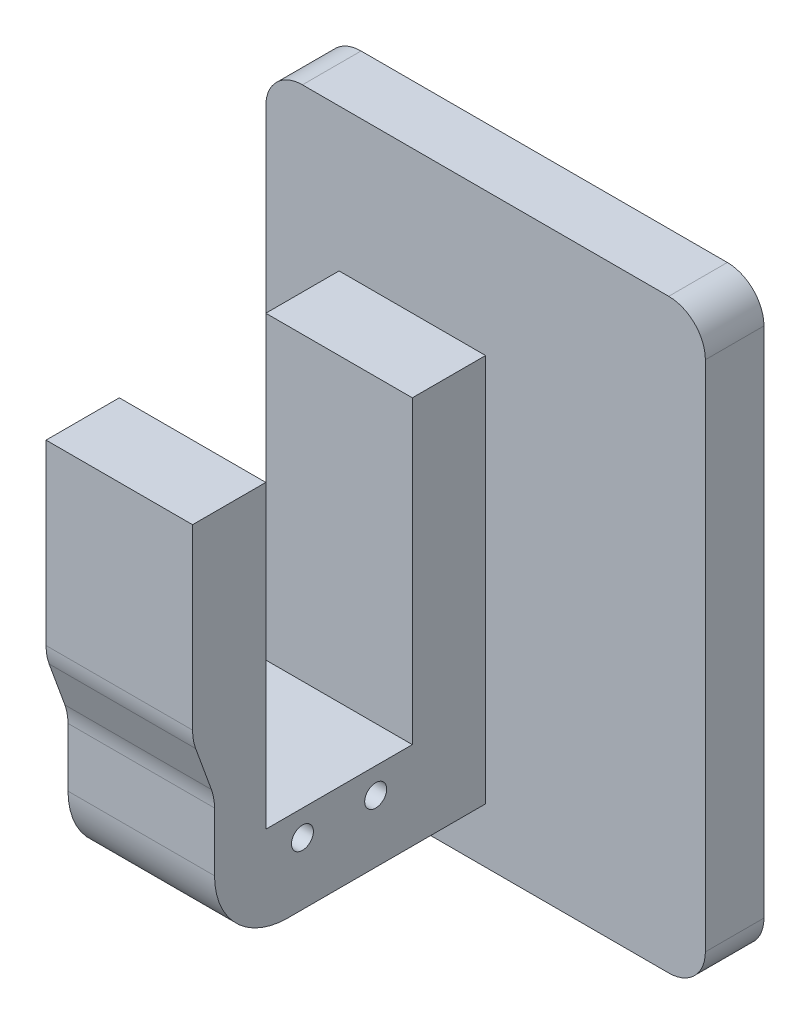
SolidWorks part; units mm, degrees
ref_plane "Front Plane" through (0, 0, 0) normal (0, 0, 1) x (1, 0, 0)
ref_plane "Top Plane" through (0, 0, 0) normal (0, 1, 0) x (1, 0, 0)
ref_plane "Right Plane" through (0, 0, 0) normal (1, 0, 0) x (0, 0, -1)
sketch "Sketch3" plane through (0, 0, 30) normal (0, 0, -1) x (-1, 0, 0)
  line L0 (95, 33.2573) -> (65, 33.2573) construction
  line L15 (80, 53.2573) -> (80, 33.2573) construction
  line L20 (55, 53.2573) -> (105, 53.2573)
  line L29 (55, -26.7427) -> (105, -26.7427)
  line L31 (110, -21.7427) -> (110, 48.2573)
  line L33 (50, -21.7427) -> (50, 48.2573)
  arc A17 (50, 48.2573) -> (55, 53.2573) centre (55, 48.2573) cw
  arc A18 (110, 48.2573) -> (105, 53.2573) centre (105, 48.2573) ccw
  arc A21 (50, -21.7427) -> (55, -26.7427) centre (55, -21.7427) ccw
  arc A22 (110, -21.7427) -> (105, -26.7427) centre (105, -21.7427) cw
  dimension "D1" = 5
extrude "Boss-Extrude1" add sketch "Sketch3" along normal blind 8
ref_plane "Plane1" through (-80, 0, 0) normal (-1, 0, 0) x (0, 0, 1)
sketch "Sketch8" plane through (0, 0, 22) normal (0, 0, -1) x (-1, 0, 0)
  line L0 (50, 13.2573) -> (110, 13.2573) construction
  line L1 (50, 48.2573) -> (50, -21.7427) construction
  line L2 (110, -21.7427) -> (110, 48.2573) construction
  line L3 (80, 13.2573) -> (80, -26.7427) construction
  line L4 (55, -26.7427) -> (105, -26.7427) construction
  line L5 (78.25, 15.3786) -> (78.25, 11.136)
  line L6 (81.75, 15.3786) -> (81.75, 11.136)
  arc A0 (78.25, 11.136) -> (81.75, 11.136) centre (80, 13.2573) ccw
  arc A1 (81.75, 15.3786) -> (78.25, 15.3786) centre (80, 13.2573) ccw
extrude "Cut-Extrude3" cut sketch "Sketch8" against normal blind 3
sketch "Sketch10" plane through (0, 0, 22) normal (0, 0, -1) x (-1, 0, 0)
  line L0 (50, 13.2573) -> (110, 13.2573) construction
  line L1 (50, 48.2573) -> (50, -21.7427) construction
  line L2 (110, -21.7427) -> (110, 48.2573) construction
  line L3 (80, 13.2573) -> (80, -26.7427) construction
  line L4 (55, -26.7427) -> (105, -26.7427) construction
  line L7 (81.75, 11.136) -> (81.75, 15.3786)
  line L8 (78.25, 15.3786) -> (78.25, 11.136)
  line L9 (81.75, 11.136) -> (81.75, 15.3786)
  line L10 (78.25, 15.3786) -> (78.25, 11.136)
  circle A3 centre (80, 13.2573) radius 9.75
  arc A5 (78.25, 11.136) -> (81.75, 11.136) centre (80, 13.2573) ccw
  arc A6 (81.75, 15.3786) -> (78.25, 15.3786) centre (80, 13.2573) ccw
  arc A7 (78.25, 11.136) -> (81.75, 11.136) centre (80, 13.2573) ccw
  arc A8 (81.75, 15.3786) -> (78.25, 15.3786) centre (80, 13.2573) ccw
  dimension "D1" = 0
extrude "Boss-Extrude4" add sketch "Sketch10" along normal blind 9
sketch "Sketch12" plane through (-80, 0, 0) normal (-1, 0, 0) x (0, 0, 1)
  line L0 (30, -19.2427) -> (30, 33.7573)
  line L2 (30, -21.7427) -> (30, 48.2573) construction
  line L21 (40, 33.7573) -> (40, -7.2427)
  line L22 (40, -7.2427) -> (60, -7.2427)
  line L24 (67.0011, -19.2427) -> (30, -19.2427)
  line L25 (40, -6.9927) -> (40, 33.5073) construction
  line L27 (60, -6.9927) -> (40, -6.9927) construction
  line L35 (60, 39.4573) -> (60, 33.5073) construction
  line L36 (60, 33.7573) -> (60, -7.2427)
  line L40 (60, 33.7573) -> (70, 33.7573)
  line L41 (40, 33.7573) -> (30, 33.7573)
  line L42 (70, 33.7573) -> (70, 8.2394)
  line L43 (70, 8.2394) -> (67.0011, 0)
  line L44 (67.0011, 0) -> (67.0011, -19.2427)
  point P10 (67.0011, -19.2427)
  point P21 (67.0011, -19.6293)
  dimension "D1" = 0
  dimension "D2" = 10
  dimension "D3" = 0.25
  dimension "D4" = 160
extrude "Boss-Extrude5" add sketch "Sketch12" along normal blind 20
sketch "Sketch13" plane through (-80, 0, 0) normal (1, 0, 0) x (0, 0, -1)
  circle A0 centre (-55, -10.7427) radius 1.5
  circle A1 centre (-45, -10.7427) radius 1.5
  circle A2 centre (-55, 37.2573) radius 1.5
  circle A3 centre (-45, 37.2573) radius 1.5
extrude "Cut-Extrude4" cut sketch "Sketch13" against normal blind 10
sketch "Sketch14" plane through (0, 0, 22) normal (0, 0, -1) x (-1, 0, 0)
  circle A0 centre (80, 13.2573) radius 12
extrude "Boss-Extrude6" add sketch "Sketch14" along normal blind 1
fillet "Fillet4" radius 10 1 edges at (-90, -19.2427, 67.0011)
fillet "Fillet5" radius 7 2 edges at (-90, 8.2394, 70) (-90, 0, 67.0011)
